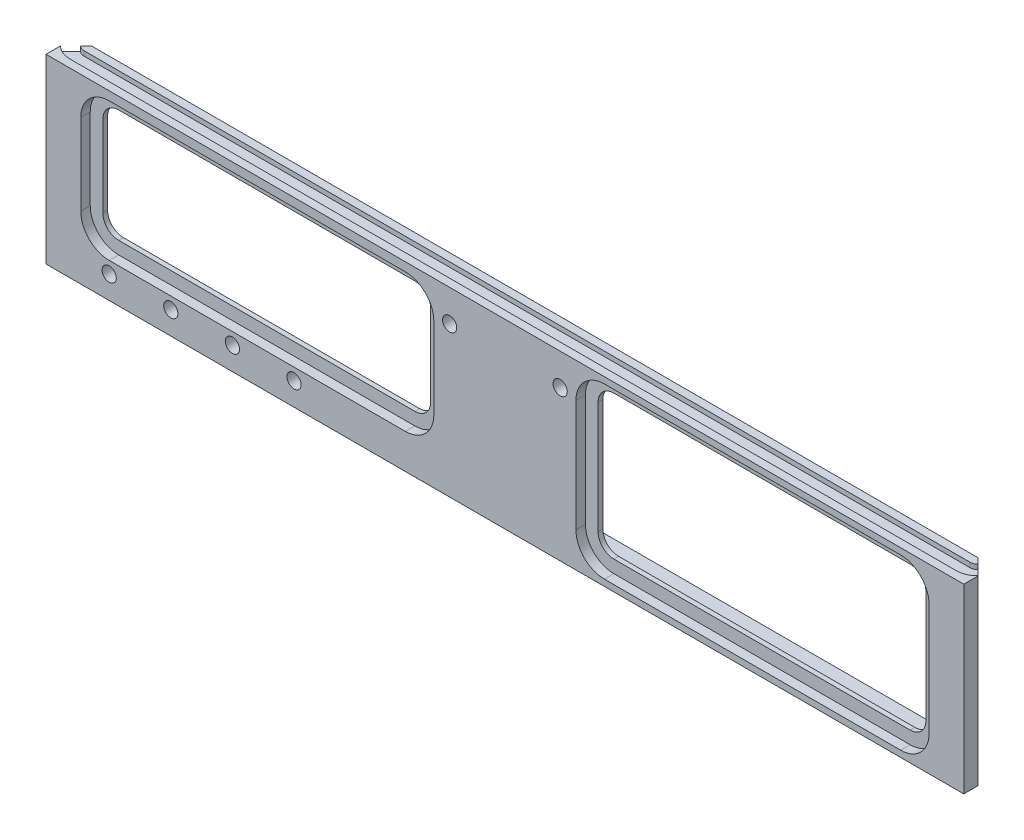
SolidWorks part; units mm, degrees
ref_plane "Front Plane" through (0, 0, 0) normal (0, 0, 1) x (1, 0, 0)
ref_plane "Top Plane" through (0, 0, 0) normal (0, 1, 0) x (1, 0, 0)
ref_plane "Right Plane" through (0, 0, 0) normal (1, 0, 0) x (0, 0, -1)
sketch "Sketch1" plane through (0, 0, 0) normal (0, 0, 1) x (1, 0, 0)
  line L1 (-290.5, 57.5) -> (290.5, 57.5)
  line L2 (-290.5, 57.5) -> (-290.5, -57.5)
  line L3 (-290.5, -57.5) -> (290.5, -57.5)
  line L4 (290.5, 57.5) -> (290.5, -57.5)
  point P5 (0, -57.5)
  dimension "D1" = 115
  dimension "D2" = 581
  dimension "D3" = 57.5
  dimension "D4" = 0
extrude "Boss-Extrude1" add sketch "Sketch1" along normal blind 9
sketch "Sketch2" plane through (0, 57.5, 0) normal (0, 1, 0) x (1, 0, 0)
  line L4 (-280.5, 10) -> (280.5, 10)
  line L5 (-290.5, 0) -> (-280.5, 10)
  line L6 (290.5, 0) -> (280.5, 10)
  line L7 (290.5, 0) -> (-290.5, 0) construction
  line L8 (-290.5, 0) -> (290.5, 0)
  dimension "D1" = 10
extrude "Boss-Extrude2" add sketch "Sketch2" against normal blind 10
sketch "Sketch3" plane through (0, 0, 9) normal (0, 0, 1) x (1, 0, 0)
  line L0 (290.5, 57.5) -> (-290.5, 57.5) construction
  line L1 (250.5, 45.5) -> (62.9918, 45.5)
  line L2 (260.5, 35.5) -> (260.5, -35.5)
  line L3 (250.5, -45.5) -> (62.9918, -45.5)
  line L4 (52.9918, 35.5) -> (52.9918, -35.5)
  line L5 (-290.5, -57.5) -> (290.5, -57.5) construction
  line L6 (290.5, -57.5) -> (290.5, 57.5) construction
  line L7 (44.9918, 43) -> (44.9918, 55.7) construction
  line L8 (-62.9918, 43.9825) -> (-250.5, 43.9825)
  line L9 (-52.9918, 33.9825) -> (-52.9918, -17.5)
  line L10 (-62.9918, -27.5) -> (-250.5, -27.5)
  line L11 (-260.5, 33.9825) -> (-260.5, -17.5)
  line L12 (-290.5, 57.5) -> (-290.5, -57.5) construction
  arc A0 (62.9918, -45.5) -> (52.9918, -35.5) centre (62.9918, -35.5) cw
  arc A1 (260.5, -35.5) -> (250.5, -45.5) centre (250.5, -35.5) cw
  arc A2 (250.5, 45.5) -> (260.5, 35.5) centre (250.5, 35.5) cw
  arc A3 (62.9918, 45.5) -> (52.9918, 35.5) centre (62.9918, 35.5) ccw
  arc A4 (-250.5, -27.5) -> (-260.5, -17.5) centre (-250.5, -17.5) cw
  arc A5 (-52.9918, -17.5) -> (-62.9918, -27.5) centre (-62.9918, -17.5) cw
  arc A6 (-62.9918, 43.9825) -> (-52.9918, 33.9825) centre (-62.9918, 33.9825) cw
  arc A7 (-250.5, 43.9825) -> (-260.5, 33.9825) centre (-250.5, 33.9825) ccw
  dimension "D5" = 10
  dimension "D6" = 10
  dimension "D1" = 12
  dimension "D2" = 12
  dimension "D3" = 30
  dimension "D4" = 8
  dimension "D7" = 30
  dimension "D8" = 30
extrude "Cut-Extrude1" cut sketch "Sketch3" against normal up to surface (9 mm away) up to face at (0, -5, 0)
sketch "Sketch5" plane through (0, 57.5, 0) normal (0, 1, 0) x (1, 0, 0)
  line L1 (-290.3995, 0.1005) -> (-284.0355, 6.4645)
  line L2 (280.5, -4) -> (-280.5, -4)
  line L3 (280.5, 5) -> (-280.5, 5)
  line L6 (-280.5, 10) -> (-290.5, 0) construction
  line L10 (290.5, 0) -> (280.5, 10) construction
  line L11 (290.3995, 0.1005) -> (284.0355, 6.4645)
  arc A4 (280.5, 5) -> (284.0355, 6.4645) centre (280.5, 10) ccw
  arc A5 (280.5, -4) -> (290.3995, 0.1005) centre (280.5, 10) ccw
  arc A6 (-280.5, 5) -> (-284.0355, 6.4645) centre (-280.5, 10) cw
  arc A7 (-280.5, -4) -> (-290.3995, 0.1005) centre (-280.5, 10) cw
extrude "Cut-Extrude3" cut sketch "Sketch5" against normal blind 3
mirror "Mirror2" about plane through (0, 0, 0) normal (0, 1, 0) of "Cut-Extrude3", "Boss-Extrude2"
sketch "Sketch10" plane through (0, 0, 9) normal (0, 0, 1) x (1, 0, 0)
  line L0 (-268.5, -17.5) -> (-268.5, 33.9825)
  line L1 (-250.5, 51.9825) -> (-62.9918, 51.9825)
  line L2 (-44.9918, 33.9825) -> (-44.9918, -17.5)
  line L3 (-62.9918, -35.5) -> (-250.5, -35.5)
  line L4 (44.9918, -35.5) -> (44.9918, 35.5)
  line L5 (62.9918, 53.5) -> (250.5, 53.5)
  line L6 (268.5, 35.5) -> (268.5, -35.5)
  line L7 (250.5, -53.5) -> (62.9918, -53.5)
  line L33 (-250.5, -35.5) -> (-62.9918, -35.5)
  line L34 (-44.9918, -17.5) -> (-44.9918, 33.9825)
  line L35 (-62.9918, 51.9825) -> (-250.5, 51.9825)
  line L36 (-268.5, 33.9825) -> (-268.5, -17.5)
  line L37 (-250.5, -35.5) -> (-62.9918, -35.5) construction
  line L38 (-44.9918, -17.5) -> (-44.9918, 33.9825) construction
  line L39 (-62.9918, 51.9825) -> (-250.5, 51.9825) construction
  line L40 (-268.5, 33.9825) -> (-268.5, -17.5) construction
  line L61 (62.9918, -53.5) -> (250.5, -53.5)
  line L62 (268.5, -35.5) -> (268.5, 35.5)
  line L63 (250.5, 53.5) -> (62.9918, 53.5)
  line L64 (44.9918, 35.5) -> (44.9918, -35.5)
  line L65 (62.9918, -53.5) -> (250.5, -53.5) construction
  line L66 (268.5, -35.5) -> (268.5, 35.5) construction
  line L67 (250.5, 53.5) -> (62.9918, 53.5) construction
  line L68 (44.9918, 35.5) -> (44.9918, -35.5) construction
  arc A0 (-268.5, 33.9825) -> (-250.5, 51.9825) centre (-250.5, 33.9825) cw
  arc A1 (-62.9918, 51.9825) -> (-44.9918, 33.9825) centre (-62.9918, 33.9825) cw
  arc A2 (-44.9918, -17.5) -> (-62.9918, -35.5) centre (-62.9918, -17.5) cw
  arc A3 (-250.5, -35.5) -> (-268.5, -17.5) centre (-250.5, -17.5) cw
  arc A4 (44.9918, 35.5) -> (62.9918, 53.5) centre (62.9918, 35.5) cw
  arc A5 (250.5, 53.5) -> (268.5, 35.5) centre (250.5, 35.5) cw
  arc A6 (268.5, -35.5) -> (250.5, -53.5) centre (250.5, -35.5) cw
  arc A7 (62.9918, -53.5) -> (44.9918, -35.5) centre (62.9918, -35.5) cw
  arc A28 (-268.5, -17.5) -> (-250.5, -35.5) centre (-250.5, -17.5) ccw
  arc A29 (-62.9918, -35.5) -> (-44.9918, -17.5) centre (-62.9918, -17.5) ccw
  arc A30 (-44.9918, 33.9825) -> (-62.9918, 51.9825) centre (-62.9918, 33.9825) ccw
  arc A31 (-250.5, 51.9825) -> (-268.5, 33.9825) centre (-250.5, 33.9825) ccw
  arc A32 (-268.5, -17.5) -> (-250.5, -35.5) centre (-250.5, -17.5) ccw construction
  arc A33 (-62.9918, -35.5) -> (-44.9918, -17.5) centre (-62.9918, -17.5) ccw construction
  arc A34 (-44.9918, 33.9825) -> (-62.9918, 51.9825) centre (-62.9918, 33.9825) ccw construction
  arc A35 (-250.5, 51.9825) -> (-268.5, 33.9825) centre (-250.5, 33.9825) ccw construction
  arc A52 (44.9918, -35.5) -> (62.9918, -53.5) centre (62.9918, -35.5) ccw
  arc A53 (250.5, -53.5) -> (268.5, -35.5) centre (250.5, -35.5) ccw
  arc A54 (268.5, 35.5) -> (250.5, 53.5) centre (250.5, 35.5) ccw
  arc A55 (62.9918, 53.5) -> (44.9918, 35.5) centre (62.9918, 35.5) ccw
  arc A56 (44.9918, -35.5) -> (62.9918, -53.5) centre (62.9918, -35.5) ccw construction
  arc A57 (250.5, -53.5) -> (268.5, -35.5) centre (250.5, -35.5) ccw construction
  arc A58 (268.5, 35.5) -> (250.5, 53.5) centre (250.5, 35.5) ccw construction
  arc A59 (62.9918, 53.5) -> (44.9918, 35.5) centre (62.9918, 35.5) ccw construction
  dimension "D1" = 8
  dimension "D2" = 8
extrude "Cut-Extrude5" cut sketch "Sketch10" against normal blind 6
sketch "Sketch11" plane through (0, 0, 9) normal (0, 0, 1) x (1, 0, 0)
  line L0 (-290.5, -47.5) -> (290.5, -47.5) construction
  line L1 (-290.5, 47.5) -> (-290.5, -47.5) construction
  circle A0 centre (-250.5, -43) radius 4.5
  circle A4 centre (-211.5, -43) radius 4.5
  circle A5 centre (-172.5, -43) radius 4.5
  circle A6 centre (-133.5, -43) radius 4.5
  dimension "D1" = 4.5
  dimension "D2" = 40
  dimension "D3" = 4
extrude "Cut-Extrude6" cut sketch "Sketch11" along direction (0, 0, -1) on the side against the normal up to surface (9 mm away) up to face at (-156.7459, 8.2412, 0)
sketch "Sketch12" plane through (0, 0, 9) normal (0, 0, 1) x (1, 0, 0)
  line L0 (-290.5, 47.5) -> (290.5, 47.5) construction
  line L1 (-44.9918, -17.5) -> (-44.9918, 33.9825) construction
  line L2 (44.9918, 35.5) -> (44.9918, -35.5) construction
  circle A0 centre (-34.9918, 37.5) radius 4.5
  circle A1 centre (34.9918, 37.5) radius 4.5
  dimension "D1" = 10
  dimension "D2" = 10
  dimension "D4" = 10
  dimension "D3" = 2
extrude "Cut-Extrude7" cut sketch "Sketch12" against normal up to surface (9 mm away) up to face at (-156.7459, 8.2412, 0)
